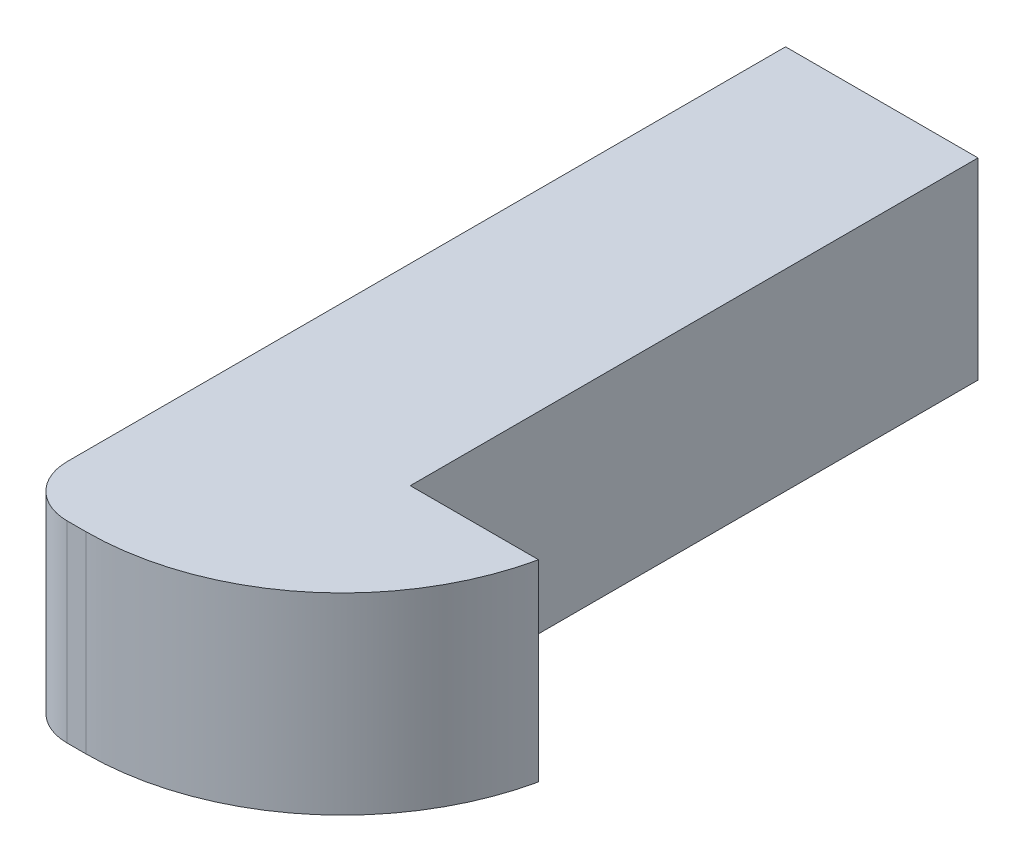
SolidWorks part; units mm, degrees
ref_plane "정면" through (0, 0, 0) normal (0, 0, 1) x (1, 0, 0)
ref_plane "윗면" through (0, 0, 0) normal (0, 1, 0) x (1, 0, 0)
ref_plane "우측면" through (0, 0, 0) normal (1, 0, 0) x (0, 0, -1)
sketch "Sketch1" plane through (0, 0, 0) normal (0, 0, 1) x (1, 0, 0)
  line L1 (0, 0) -> (-9.525, 0)
  line L2 (0, 0) -> (0, 9.525)
  line L3 (0, 9.525) -> (-9.525, 9.525)
  line L4 (-9.525, 0) -> (-9.525, 9.525)
  dimension "D1" = 9.525
  dimension "D2" = 9.525
extrude "Extrude1" add sketch "Sketch1" along normal blind 38.1
hole_wizard "1/4-20 Tapped Hole1" positions "3DSketch4" profile "Sketch7" tap size "1/4-20" standard "Ansi Inch"
sketch3d "3DSketch4"
  line L2 (-9.525, 9.525, 0) -> (-9.525, 0, 0) construction
  line L3 (-9.525, 0, 0) -> (0, 0, 0) construction
  point P9 (-4.7625, 4.7625, 0)
  dimension "D1" = 4.7625
  dimension "D2" = 4.7625
sketch "Sketch7" plane through (-4.7625, 4.7625, 0) normal (1, 0, 0) x (0, 1, 0)
  line L0 (0, 0) -> (0, 22.8698)
  line L1 (0, 22.8698) -> (2.5527, 21.336)
  line L2 (2.5527, 21.336) -> (2.5527, 14.986)
  line L3 (2.5527, 14.986) -> (3.175, 14.986)
  line L4 (3.175, 14.986) -> (3.175, 0)
  line L5 (3.175, 0) -> (0, 0)
  line L10 (0, 22.8698) -> (-2.5527, 21.336) construction
  line L11 (0, -6.35) -> (0, 107.95) construction
  dimension "Tap Drill Dia." = 5.1054
  dimension "Tap Drill Depth" = 21.336
  dimension "Thread Major Dia." = 6.35
  dimension "Thread Depth" = 14.986
  dimension "Drill Angle" = 118
sketch "Sketch9" plane through (0, 0, 0) normal (1, 0, 0) x (0, 0, -1)
  line L0 (-38.1, 0) -> (0, 0) construction
  line L1 (-38.1, 9.525) -> (-28.1, 9.525)
  line L2 (-38.1, 9.525) -> (-38.1, 0)
  line L3 (-38.1, 0) -> (-28.1, 0)
  line L4 (-28.1, 9.525) -> (-28.1, 0)
  dimension "D1" = 10
extrude "Extrude3" add sketch "Sketch9" along normal blind 6.35
fillet "Fillet2" radius 12.7 1 edges at (6.35, 4.7625, 38.1)
fillet "Fillet3" radius 2.54 1 edges at (-9.525, 4.7625, 38.1)
